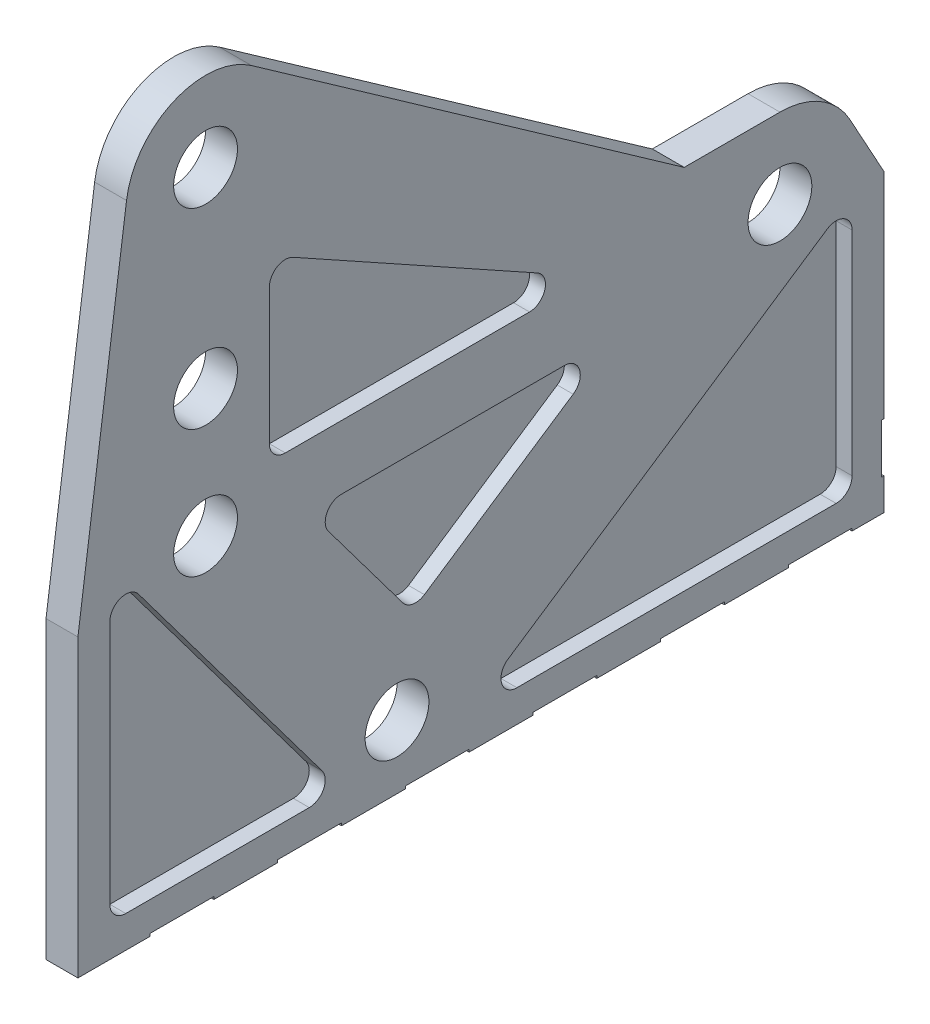
SolidWorks part; units mm, degrees
material "7075-T6 (SN)"
ref_plane "Front Plane" through (0, 0, 0) normal (0, 0, 1) x (1, 0, 0)
ref_plane "Top Plane" through (0, 0, 0) normal (0, 1, 0) x (1, 0, 0)
ref_plane "Right Plane" through (0, 0, 0) normal (1, 0, 0) x (0, 0, -1)
sketch "Sketch1" plane through (0, 0, 0) normal (1, 0, 0) x (0, 0, -1)
  line L0 (0, 44.45) -> (0, 0) construction
  line L1 (-279.4, 44.45) -> (279.4, 44.45)
  line L2 (-279.4, 44.45) -> (-279.4, -44.45)
  line L3 (-279.4, -44.45) -> (279.4, -44.45)
  line L4 (279.4, 44.45) -> (279.4, -44.45)
  line L5 (0, 0) -> (279.4, 0) construction
  dimension "D1" = 558.8
  dimension "D2" = 88.9
extrude "Boss-Extrude1" add sketch "Sketch1" along normal blind 12.7 contours L4 L1 L2 L3 region at (0, 0, 0)
sketch "Sketch2" plane through (12.7, 0, 0) normal (1, 0, 0) x (0, 0, -1)
  line L0 (-279.4, -44.45) -> (279.4, -44.45) construction
  line L1 (-279.4, 44.45) -> (-226.9595, 103.6106)
  line L2 (82.55, 44.45) -> (53.2287, 97.8348)
  line L3 (-203.2, 114.3) -> (25.4, 114.3)
  line L4 (-279.4, 44.45) -> (82.55, 44.45)
  line L5 (-279.4, 44.45) -> (279.4, 44.45) construction
  line L6 (279.4, 44.45) -> (279.4, -44.45) construction
  line L7 (-279.4, 44.45) -> (-318.8009, 0) construction
  line L8 (-318.8009, 0) -> (-279.4, -44.45) construction
  line L9 (-279.4, 44.45) -> (-279.4, -44.45) construction
  line L10 (-279.4, -44.45) -> (-279.4, 0) construction
  line L11 (-279.4, 0) -> (-318.8009, 0) construction
  circle A0 centre (-203.2, 82.55) radius 12.7
  circle A1 centre (25.4, 82.55) radius 12.7
  circle A2 centre (-203.2, 82.55) radius 31.75
  circle A3 centre (25.4, 82.55) radius 31.75
  line M2 (279.4, 44.45) -> (-279.4, 44.45)
  dimension "D1" = 25.4
  dimension "D2" = 63.5
  dimension "D3" = 127
  dimension "D4" = 127
  dimension "D5" = 228.6
  dimension "D6" = 254
  dimension "D7" = 196.85
extrude "Boss-Extrude2" add sketch "Sketch2" against normal blind 12.7 contours A3 L3 A2 L1 L2 M2 | A2 A0 | A3 A1 region at (12.7, 75.2348, 94.7711) region at (12.7, 110.6856, 215.8582) region at (12.7, 90.2167, -55.2842)
sketch "Sketch3" plane through (12.7, 0, 0) normal (1, 0, 0) x (0, 0, -1)
  line L0 (-279.4, -44.45) -> (-318.8009, 0)
  line L1 (-318.8009, 0) -> (-279.4, 44.45)
  line L2 (-279.4, 44.45) -> (-279.4, -44.45)
  line L3 (-318.8009, 0) -> (-279.4, 0) construction
  line L4 (-279.4, 44.45) -> (-226.9595, 103.6106) construction
extrude "Boss-Extrude3" add sketch "Sketch3" against normal blind 12.7
sketch "Sketch4" plane through (12.7, 0, 0) normal (1, 0, 0) x (0, 0, -1)
  line L0 (82.55, 44.45) -> (106.9639, 0)
  line L1 (106.9639, 0) -> (82.55, -44.45)
  line L2 (-279.4, -44.45) -> (279.4, -44.45) construction
  line L3 (0, 0) -> (106.9639, 0) construction
  line L4 (82.55, 44.45) -> (53.2287, 97.8348) construction
  line L5 (82.55, 44.45) -> (279.4, 44.45)
  line L6 (279.4, 44.45) -> (279.4, -44.45)
  line L7 (279.4, -44.45) -> (82.55, -44.45)
  line L8 (82.55, 44.45) -> (82.55, -44.45) construction
extrude "Cut-Extrude1" cut sketch "Sketch4" against normal through all
sketch "Sketch5" plane through (12.7, 0, 0) normal (1, 0, 0) x (0, 0, -1)
  line L0 (-254, -44.45) -> (-254, 73.1049)
  line L1 (-279.4, -44.45) -> (82.55, -44.45) construction
  line L2 (-318.8009, 0) -> (-226.9595, 103.6106) construction
  line L3 (-254, 73.1049) -> (66.8114, 73.1049) construction
  line L4 (-254, -44.45) -> (-279.4, -44.45)
  line L5 (-279.4, -44.45) -> (-318.8009, 0)
  line L6 (-318.8009, 0) -> (-254, 73.1049)
  line L7 (66.8114, 73.1049) -> (66.8114, -44.45)
  line L8 (106.9639, 0) -> (53.2287, 97.8348) construction
  line L9 (66.8114, -44.45) -> (82.55, -44.45)
  line L10 (82.55, -44.45) -> (106.9639, 0)
  line L11 (106.9639, 0) -> (66.8114, 73.1049)
  circle A0 centre (-203.2, 82.55) radius 12.7 construction
  dimension "D1" = 50.8
extrude "Cut-Extrude2" cut sketch "Sketch5" against normal through all
sketch "Sketch6" plane through (12.7, 0, 0) normal (1, 0, 0) x (0, 0, -1)
  line L0 (-254, 73.1049) -> (-234.6544, 213.8728)
  line L2 (-254, 73.1049) -> (-226.9595, 103.6106)
  line L3 (-226.9595, 103.6106) -> (-203.2, 114.3)
  line L4 (-203.2, 114.3) -> (-12.7, 114.3)
  line L5 (-203.2, 114.3) -> (25.4, 114.3) construction
  line L6 (-12.7, 114.3) -> (-184.9263, 235.5141)
  line L7 (-203.2, 133.35) -> (-203.2, 82.55) construction
  circle A0 centre (-203.2, 133.35) radius 12.7
  circle A1 centre (-203.2, 209.55) radius 12.7
  circle A2 centre (-203.2, 82.55) radius 12.7 construction
  circle A4 centre (-203.2, 209.55) radius 31.75
  circle A5 centre (-203.2, 133.35) radius 31.75
  line M4 (25.4, 114.3) -> (-203.2, 114.3)
  arc M5 (-203.2, 114.3) -> (-226.9595, 103.6106) centre (-203.2, 82.55) ccw
  line M6 (-226.9595, 103.6106) -> (-254, 73.1049)
  dimension "D1" = 25.4
  dimension "D3" = 50.8
  dimension "D5" = 63.5
  dimension "D2" = 76.2
  dimension "D6" = 190.5
extrude "Boss-Extrude4" add sketch "Sketch6" against normal blind 12.7 contours A5 L2 | A5 A0 M6 M5 | A5 L6 A4 M4 | A4 A1 region at (12.7, 151.5039, 143.957) region at (12.7, 237.8392, 215.5113) region at (12.7, 160.9839, 217.017)
sketch "Sketch7" plane through (12.7, 0, 0) normal (1, 0, 0) x (0, 0, -1)
  line L0 (-254, -44.45) -> (66.8114, -44.45) construction
  line L1 (-254, -44.45) -> (-254, 73.1049) construction
  circle A0 centre (-127, -19.05) radius 12.7
  dimension "D1" = 25.4
  dimension "D2" = 25.4
  dimension "D3" = 127
extrude "Cut-Extrude3" cut sketch "Sketch7" against normal through all
sketch "Sketch8" plane through (12.7, 0, 0) normal (1, 0, 0) x (0, 0, -1)
  line L0 (-203.2, 82.55) -> (-127, -19.05) construction
  line L1 (-127, -19.05) -> (25.4, 82.55) construction
  line L2 (25.4, 82.55) -> (-203.2, 82.55) construction
  line L3 (-203.2, 82.55) -> (-203.2, 133.35) construction
  line L4 (-203.2, 133.35) -> (-203.2, 209.55) construction
  line L5 (-203.2, 209.55) -> (25.4, 82.55) construction
  line L6 (-229.87, 75.7767) -> (-156.845, -21.59)
  line L7 (-82.8092, -20.1165) -> (44.2391, 64.5824)
  line L8 (-74.2673, 95.25) -> (-171.45, 95.25)
  line L9 (-177.8, 101.6) -> (-177.8, 133.35)
  line L10 (-177.8, 133.35) -> (-177.8, 155.5904)
  line L11 (-168.3662, 161.1413) -> (-71.1834, 107.1509)
  line L12 (-154.305, 59.69) -> (-124.701, 20.2181)
  line L13 (-116.0987, 18.7445) -> (-56.8908, 58.2165)
  line L14 (-60.4131, 69.85) -> (-149.225, 69.85)
  line L18 (-121.0968, 15.4124) -> (11.3106, 103.6841) construction
  line L19 (-182.88, 97.79) -> (-121.0968, 15.4124) construction
  line L20 (25.4, 69.85) -> (-203.2, 69.85) construction
  line L21 (-177.8, 166.3823) -> (13.0647, 60.3464) construction
  line L22 (-177.8, 133.35) -> (-177.8, 166.3823) construction
  line L23 (25.4, 95.25) -> (-203.2, 95.25) construction
  line L24 (-177.8, 82.55) -> (-177.8, 133.35) construction
  line L37 (-161.925, -31.75) -> (-234.95, -31.75)
  line L38 (-132.9032, -53.5124) -> (39.4894, 61.4159) construction
  line L39 (-223.52, 67.31) -> (-132.9032, -53.5124) construction
  line L40 (54.1114, 73.1049) -> (54.1114, -31.75)
  line L41 (54.1114, -31.75) -> (-241.3, -31.75)
  line L42 (-241.3, -31.75) -> (-241.3, 73.1049)
  line L43 (54.1114, 59.2989) -> (54.1114, -25.4)
  line L44 (47.7614, -31.75) -> (-79.2869, -31.75)
  line L45 (-241.3, -25.4) -> (-241.3, 71.9667)
  arc A0 (-116.0987, 18.7445) -> (-124.701, 20.2181) centre (-119.621, 24.0281) cw
  arc A1 (-154.305, 59.69) -> (-149.225, 69.85) centre (-149.225, 63.5) cw
  arc A2 (-56.8908, 58.2165) -> (-60.4131, 69.85) centre (-60.4131, 63.5) ccw
  arc A3 (-168.3662, 161.1413) -> (-177.8, 155.5904) centre (-171.45, 155.5904) ccw
  arc A4 (-74.2673, 95.25) -> (-71.1834, 107.1509) centre (-74.2673, 101.6) ccw
  arc A5 (-171.45, 95.25) -> (-177.8, 101.6) centre (-171.45, 101.6) cw
  arc A6 (-241.3, 71.9667) -> (-229.87, 75.7767) centre (-234.95, 71.9667) cw
  arc A7 (54.1114, 59.2989) -> (44.2391, 64.5824) centre (47.7614, 59.2989) ccw
  arc A8 (54.1114, -25.4) -> (47.7614, -31.75) centre (47.7614, -25.4) cw
  arc A9 (-79.2869, -31.75) -> (-82.8092, -20.1165) centre (-79.2869, -25.4) cw
  arc A10 (-161.925, -31.75) -> (-156.845, -21.59) centre (-161.925, -25.4) ccw
  arc A11 (-234.95, -31.75) -> (-241.3, -25.4) centre (-234.95, -25.4) cw
  dimension "D5" = 6.35
  dimension "D7" = 6.35
  dimension "D1" = 25.4
  dimension "D2" = 25.4
  dimension "D3" = 12.7
  dimension "D4" = 12.7
  dimension "D6" = 12.7
extrude "Cut-Extrude4" cut sketch "Sketch8" against normal blind 6.35
sketch "Sketch9" plane through (12.7, 0, 0) normal (1, 0, 0) x (0, 0, -1)
  line L0 (-254, -44.45) -> (66.8114, -44.45) construction
  line L1 (54.1114, -44.45) -> (28.7114, -44.45)
  line L2 (54.1114, -44.45) -> (54.1114, -43.434)
  line L3 (54.1114, -43.434) -> (28.7114, -43.434)
  line L4 (28.7114, -44.45) -> (28.7114, -43.434)
  line L5 (66.8114, 73.1049) -> (66.8114, -44.45) construction
  line L6 (3.3114, -43.434) -> (-22.0886, -43.434)
  line L7 (3.3114, -44.45) -> (-22.0886, -44.45)
  line L8 (-22.0886, -44.45) -> (-22.0886, -43.434)
  line L9 (3.3114, -44.45) -> (3.3114, -43.434)
  line L10 (-47.4886, -43.434) -> (-72.8886, -43.434)
  line L11 (-47.4886, -44.45) -> (-72.8886, -44.45)
  line L12 (-72.8886, -44.45) -> (-72.8886, -43.434)
  line L13 (-47.4886, -44.45) -> (-47.4886, -43.434)
  line L14 (-98.2886, -43.434) -> (-123.6886, -43.434)
  line L15 (-98.2886, -44.45) -> (-123.6886, -44.45)
  line L16 (-123.6886, -44.45) -> (-123.6886, -43.434)
  line L17 (-98.2886, -44.45) -> (-98.2886, -43.434)
  line L18 (-149.0886, -43.434) -> (-174.4886, -43.434)
  line L19 (-149.0886, -44.45) -> (-174.4886, -44.45)
  line L20 (-174.4886, -44.45) -> (-174.4886, -43.434)
  line L21 (-149.0886, -44.45) -> (-149.0886, -43.434)
  line L22 (-199.8886, -43.434) -> (-225.2886, -43.434)
  line L23 (-199.8886, -44.45) -> (-225.2886, -44.45)
  line L24 (-225.2886, -44.45) -> (-225.2886, -43.434)
  line L25 (-199.8886, -44.45) -> (-199.8886, -43.434)
  dimension "D1" = 12.7
  dimension "D2" = 25.4
  dimension "D3" = 1.016
  dimension "D4" = 6
extrude "Cut-Extrude5" cut sketch "Sketch9" against normal through all
sketch "Sketch10" plane through (12.7, 0, 0) normal (1, 0, 0) x (0, 0, -1)
  line L0 (66.8114, 73.1049) -> (66.8114, -44.45) construction
  line L1 (66.8114, -31.75) -> (65.7954, -31.75)
  line L2 (66.8114, -31.75) -> (66.8114, -12.065)
  line L3 (66.8114, -12.065) -> (65.7954, -12.065)
  line L4 (65.7954, -31.75) -> (65.7954, -12.065)
  line L5 (54.1114, -44.45) -> (66.8114, -44.45) construction
  dimension "D1" = 19.685
  dimension "D2" = 1.016
  dimension "D3" = 12.7
extrude "Cut-Extrude6" cut sketch "Sketch10" against normal through all
